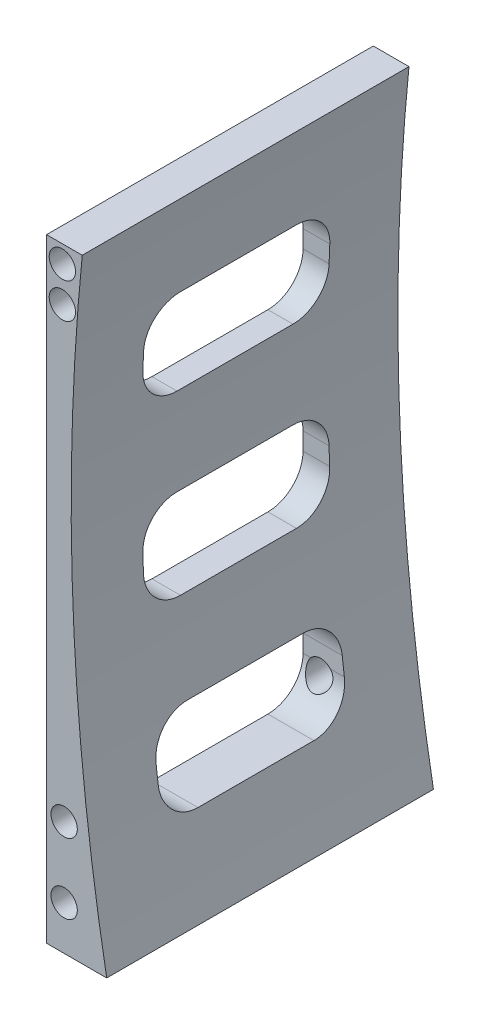
SolidWorks part; units mm, degrees
material "ABS"
ref_plane "Plano frontal" through (0, 0, 0) normal (0, 0, 1) x (1, 0, 0)
ref_plane "Plano superior" through (0, 0, 0) normal (0, 1, 0) x (1, 0, 0)
ref_plane "Plano direito" through (0, 0, 0) normal (1, 0, 0) x (0, 0, -1)
sketch "Esboço1" plane through (0, 0, 0) normal (0, 0, 1) x (1, 0, 0)
  line L0 (10, 0) -> (20, 0)
  line L1 (-20, 0) -> (-10, 0)
  line L2 (-16.3694, 93.6521) -> (-16.5765, 95.0244)
  arc A0 (-10, 0) -> (10, 0) centre (0, 0) ccw
  arc A1 (20, 0) -> (14.8299, 81.415) centre (263.5691, 56.3389) cw
  arc A2 (-20, 0) -> (-16.3694, 93.6521) centre (-263.5691, 56.3389) ccw
  arc A3 (14.8299, 81.415) -> (-16.4879, 94.4373) centre (3.2416, 97.7156) ccw
  dimension "D1" = 20
  dimension "D5" = 250
  dimension "D6" = 250
  dimension "D2" = 40
extrude "Ressalto-extrusão1" add sketch "Esboço1" along normal blind 37.2 contours A1 A3 L2 A2 L1 A0 L0 region at (0.9197, 55.6964, 0)
fillet "Filete3" radius 10 2 edges at (20, 0, 18.6) (-20, 0, 18.6)
fillet "Filete4" radius 10 2 edges at (-10, 0, 18.6) (10, 0, 18.6)
sketch "Esboço3" plane through (0, 0, 37.2) normal (0, 0, 1) x (1, 0, 0)
  line L1 (-34.3661, -10.4864) -> (30.1278, -10.4864)
  line L2 (-34.3661, -10.4864) -> (-34.3661, 11.5417)
  line L3 (-34.3661, 11.5417) -> (30.1278, 11.5417)
  line L4 (30.1278, -10.4864) -> (30.1278, 11.5417)
  dimension "D1" = 0
extrude "Corte-extrusão2" cut sketch "Esboço3" against normal through all
sketch "Esboço4" plane through (0, 0, 37.2) normal (0, 0, 1) x (1, 0, 0)
  line L0 (17.6155, 11.5417) -> (-17.6155, 11.5417) construction
  line L1 (-45.93, 11.5417) -> (10.7676, 11.5417)
  line L2 (-45.93, 11.5417) -> (-45.93, 134.6613)
  line L3 (-45.93, 134.6613) -> (10.7676, 134.6613)
  line L4 (10.7676, 11.5417) -> (10.7676, 134.6613)
  arc A1 (14.8299, 81.415) -> (17.6155, 11.5417) centre (263.5691, 56.3389) ccw construction
  point P9 (13.7676, 46.3805)
  dimension "D1" = 3
extrude "Corte-extrusão6" cut sketch "Esboço4" against normal through all
sketch "Esboço7" plane through (0, 0, 37.2) normal (0, 0, 1) x (1, 0, 0)
  line L1 (10.7676, 116.2455) -> (36.5295, 116.2455)
  line L2 (10.7676, 116.2455) -> (10.7676, 81.415)
  line L3 (10.7676, 81.415) -> (36.5295, 81.415)
  line L4 (36.5295, 116.2455) -> (36.5295, 81.415)
extrude "Corte-extrusão7" cut sketch "Esboço7" against normal through all
sketch "Esboço8" plane through (10.7676, 0, 0) normal (-1, 0, 0) x (0, 0, 1)
  line L0 (0, 11.5417) -> (37.2, 11.5417) construction
  line L1 (12, 71.415) -> (25.2, 71.415)
  line L2 (8, 67.415) -> (8, 65.415)
  line L3 (12, 61.415) -> (25.2, 61.415)
  line L4 (29.2, 67.415) -> (29.2, 65.415)
  line L5 (12, 51.475) -> (25.2, 51.475)
  line L6 (8, 47.475) -> (8, 45.475)
  line L7 (12, 41.475) -> (25.2, 41.475)
  line L8 (29.2, 47.475) -> (29.2, 45.475)
  line L9 (12, 31.5417) -> (25.2, 31.5417)
  line L10 (8, 27.5417) -> (8, 25.5417)
  line L11 (12, 21.5417) -> (25.2, 21.5417)
  line L12 (29.2, 27.5417) -> (29.2, 25.5417)
  line L13 (0, 81.415) -> (37.2, 81.415) construction
  line L14 (37.2, 11.5417) -> (37.2, 81.415) construction
  line L15 (0, 11.5417) -> (0, 81.415) construction
  arc A0 (25.2, 21.5417) -> (29.2, 25.5417) centre (25.2, 25.5417) ccw
  arc A1 (25.2, 31.5417) -> (29.2, 27.5417) centre (25.2, 27.5417) cw
  arc A2 (8, 25.5417) -> (12, 21.5417) centre (12, 25.5417) ccw
  arc A3 (12, 31.5417) -> (8, 27.5417) centre (12, 27.5417) ccw
  arc A4 (12, 51.475) -> (8, 47.475) centre (12, 47.475) ccw
  arc A5 (8, 45.475) -> (12, 41.475) centre (12, 45.475) ccw
  arc A6 (25.2, 41.475) -> (29.2, 45.475) centre (25.2, 45.475) ccw
  arc A7 (25.2, 51.475) -> (29.2, 47.475) centre (25.2, 47.475) cw
  arc A8 (25.2, 61.415) -> (29.2, 65.415) centre (25.2, 65.415) ccw
  arc A9 (25.2, 71.415) -> (29.2, 67.415) centre (25.2, 67.415) cw
  arc A10 (12, 71.415) -> (8, 67.415) centre (12, 67.415) ccw
  arc A11 (8, 65.415) -> (12, 61.415) centre (12, 65.415) ccw
  dimension "D14" = 4
  dimension "D1" = 10
  dimension "D2" = 10
  dimension "D3" = 10
  dimension "D4" = 10
  dimension "D5" = 10
  dimension "D6" = 8
  dimension "D7" = 8
  dimension "D8" = 8
  dimension "D9" = 8
  dimension "D10" = 8
  dimension "D11" = 8
  dimension "D12" = 9.94
  dimension "D13" = 9.9332
extrude "Corte-extrusão8" cut sketch "Esboço8" against normal through all
sketch "Esboço9" plane through (0, 0, 0) normal (0, 0, -1) x (-1, 0, 0)
  line L0 (-10.7676, 81.415) -> (-14.8299, 81.415) construction
  line L1 (-10.7676, 11.5417) -> (-10.7676, 81.415) construction
  line L2 (-17.6155, 11.5417) -> (-10.7676, 11.5417) construction
  circle A0 centre (-12.7676, 16.5417) radius 1.5
  circle A1 centre (-12.7676, 24.5417) radius 1.5
  circle A2 centre (-12.5676, 79.415) radius 1.5
  circle A3 centre (-12.5676, 75.415) radius 1.5
  dimension "D1" = 2
  dimension "D2" = 1.8
  dimension "D3" = 3
  dimension "D4" = 1.8
  dimension "D5" = 3
  dimension "D6" = 4
  dimension "D7" = 2
  dimension "D8" = 2
  dimension "D9" = 5
  dimension "D10" = 8
  dimension "D11" = 3
  dimension "D12" = 3
extrude "Corte-extrusão9" cut sketch "Esboço9" against normal through all
